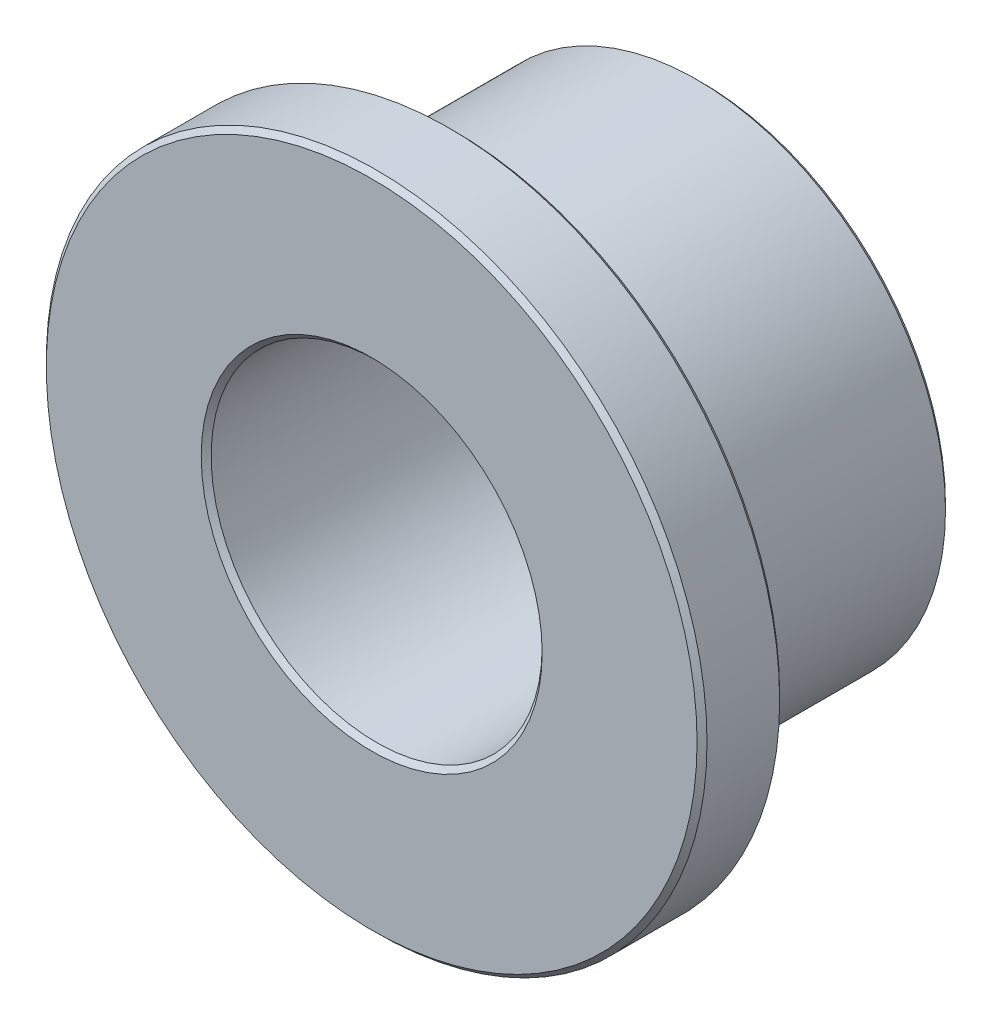
SolidWorks part; units mm, degrees
ref_plane "Front" through (0, 0, 0) normal (0, 0, 1) x (1, 0, 0)
ref_plane "Top" through (0, 0, 0) normal (0, 1, 0) x (1, 0, 0)
ref_plane "Right" through (0, 0, 0) normal (1, 0, 0) x (0, 0, -1)
sketch "Sketch1" plane through (0, 0, 0) normal (0, 0, 1) x (1, 0, 0)
  circle A0 centre (0, 0) radius 6.3627
  circle A1 centre (0, 0) radius 9.5504
  circle A2 centre (0, 0) radius 12.7
  dimension "ID" = 12.7254
  dimension "OD" = 19.1008
  dimension "Flange OD" = 25.4
sketch "Sketch2" plane through (0, 0, 0) normal (1, 0, 0) x (0, 0, -1)
  line L0 (-6.35, -12.7) -> (6.35, -12.7) construction
  line L1 (0, 12.7) -> (0, -12.7) construction
  line L3 (-3.175, 9.5504) -> (6.35, 9.5504) construction
  point P3 (0, -12.7)
  point P7 (0, 9.5504)
  point P9 (-3.175, -12.7)
  point P10 (-6.35, 12.7)
  point P23 (0, 12.7)
  dimension "Flange Thickness" = 3.175
  dimension "Length" = 12.7
sketch "Sketch3" plane through (0, 0, 0) normal (0, 0, 1) x (1, 0, 0)
  circle A0 centre (0, 0) radius 12.7 construction
  circle A1 centre (0, 0) radius 12.7
  circle A2 centre (0, 0) radius 6.3627 construction
  circle A3 centre (0, 0) radius 6.3627
extrude "Boss-Extrude1" add sketch "Sketch3" against normal up to vertex (-3.175 mm away) from vertex up to point (0, -12.7, 3.175) starting at point (0, -12.7, 6.35)
sketch "Sketch4" plane through (0, 0, 0) normal (0, 0, 1) x (1, 0, 0)
  circle A0 centre (0, 0) radius 6.3627 construction
  circle A1 centre (0, 0) radius 9.5504 construction
  circle A2 centre (0, 0) radius 6.3627
  circle A3 centre (0, 0) radius 9.5504
extrude "Boss-Extrude2" add sketch "Sketch4" against normal up to vertex (6.35 mm away) from vertex up to point (0, 9.5504, -6.35) starting at point (0, -12.7, 3.175)
chamfer "Chamfer1" distance 0.1909 angle 45 6 edges at (6.3627, 0, 6.35) (12.7, 0, 6.35) (12.7, 0, 3.175) (9.5504, 0, 3.175) (6.3627, 0, -6.35) (9.5504, 0, -6.35)
equation "\"D1@Chamfer1\"=\"ID@Sketch1\"*0.015"
